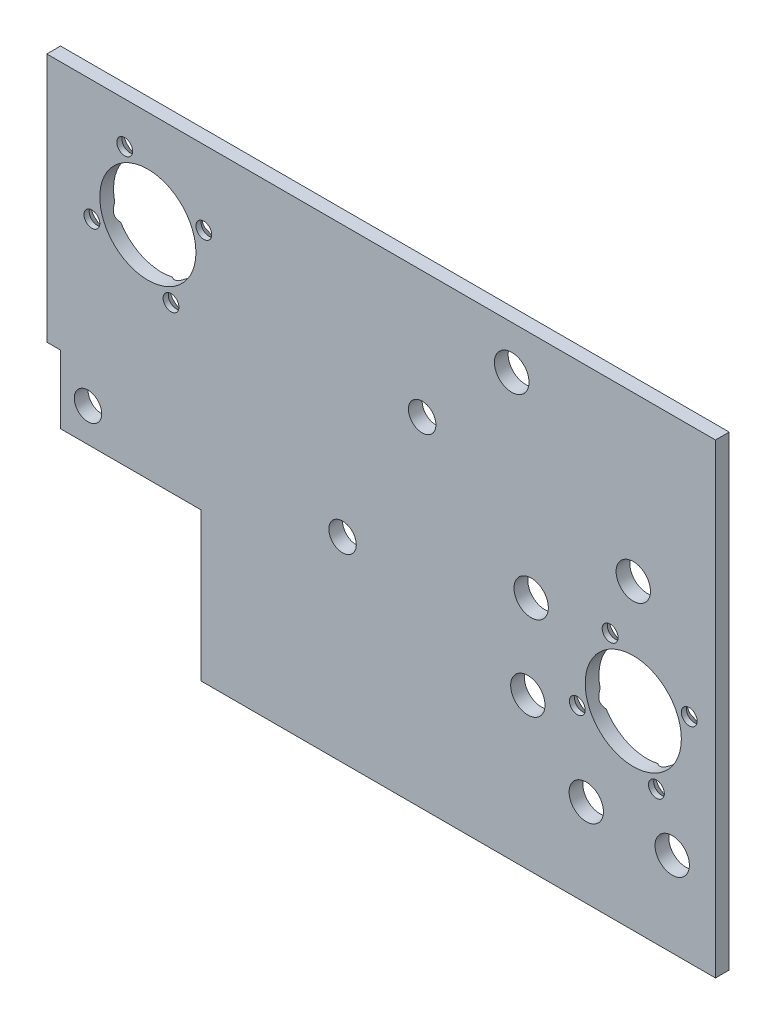
SolidWorks part; units mm, degrees
material "6061-T6 (SS)"
ref_plane "Front" through (0, 0, 0) normal (0, 0, 1) x (1, 0, 0)
ref_plane "Top" through (0, 0, 0) normal (0, 1, 0) x (1, 0, 0)
ref_plane "Right" through (0, 0, 0) normal (1, 0, 0) x (0, 0, -1)
ref_axis "side-side" through (80.9, 0, 0) along (-1, 0, 0)
ref_axis "up-down" through (0, 50, 0) along (0, -1, 0)
ref_axis "front-back" through (0, 0, -80.9) along (0, 0, 1)
sketch "Sketch2" plane through (0, 0, 0) normal (0, 0, 1) x (1, 0, 0)
  line L1 (70.9123, -1.5429) -> (62.6056, 2.3306)
  line L2 (62.6056, 2.3306) -> (55.0977, -2.9265)
  line L3 (55.0977, -2.9265) -> (55.8965, -12.0571)
  line L4 (55.8965, -12.0571) -> (64.2032, -15.9306)
  line L5 (64.2032, -15.9306) -> (71.7111, -10.6735)
  line L12 (71.7111, -10.6735) -> (70.9123, -1.5429)
  line L13 (50, 0) -> (-50, 0) construction
  line L18 (37.0625, -35.4173) -> (37.0625, -44.5827)
  line L19 (45, -30.8346) -> (37.0625, -35.4173)
  line L20 (52.9375, -35.4173) -> (45, -30.8346)
  line L21 (52.9375, -44.5827) -> (52.9375, -35.4173)
  line L22 (45, -49.1654) -> (52.9375, -44.5827)
  line L23 (37.0625, -44.5827) -> (45, -49.1654)
  line L30 (-20.1841, -46.8662) -> (-13.8341, -50.5323)
  line L31 (-20.1841, -39.5338) -> (-20.1841, -46.8662)
  line L32 (-13.8341, -35.8677) -> (-20.1841, -39.5338)
  line L33 (-7.4841, -39.5338) -> (-13.8341, -35.8677)
  line L34 (-7.4841, -46.8662) -> (-7.4841, -39.5338)
  line L35 (-13.8341, -50.5323) -> (-7.4841, -46.8662)
  line L38 (-20.1841, -57.2) -> (-20.1841, -35.2)
  line L39 (-20.1841, -35.2) -> (-23.3591, -35.2)
  line L41 (-23.3591, 24.85) -> (-23.3591, -35.2)
  line L43 (-17.6841, -85.2) -> (393.3159, -85.2)
  line L50 (-20.1841, -51.2) -> (-18.1841, -51.2)
  line L51 (9.8159, -51.2) -> (11.8159, -51.2)
  line L55 (9.8159, -81.2) -> (9.8159, -53.7)
  line L56 (-18.1841, -81.2) -> (9.8159, -81.2)
  line L57 (-18.1841, -53.7) -> (-18.1841, -81.2)
  line L61 (-20.1841, -80.7) -> (-20.1841, -53.7)
  line L62 (9.3159, -83.2) -> (-17.6841, -83.2)
  line L63 (11.8159, -80.7) -> (11.8159, -53.7)
  circle A2 centre (112.2, -41.275) radius 17.272
  circle A3 centre (45, -40) radius 3.175
  circle A5 centre (-13.8341, -43.2) radius 3.175
  circle A6 centre (125.1364, -35.9226) radius 1.25
  circle A7 centre (63.4044, -6.8) radius 7.9375 construction
  circle A9 centre (106.8476, -28.3386) radius 1.25
  circle A13 centre (84.1028, 12.5) radius 4
  circle A22 centre (137.9182, -37.5962) radius 2.6162
  circle A24 centre (127.7842, -20.4882) radius 2.6162
  point P1 (0, 0)
  point P39 (0, 0)
  point P42 (0, 0)
  point P47 (0, 0)
  dimension "D1" = 15.875
  dimension "D2" = 35
sketch "Sketch1" plane through (0, 0, 0) normal (0, 0, 1) x (1, 0, 0)
  line L0 (142.0908, -41.7813) -> (132.1091, -24.584) construction
  line L1 (0, 0) -> (-28.1303, 0) construction
  line L2 (-23.3591, 24.85) -> (-23.3591, -35.2) construction
  line L3 (-23.3591, 22.5) -> (131.2, 22.5)
  line L4 (-23.3591, -35.2) -> (-23.3591, 22.5)
  line L5 (131.2, 22.5) -> (131.2, -85.2)
  line L6 (12.3159, -85.2) -> (131.2, -85.2)
  line L7 (-20.1841, -57.2) -> (-20.1841, -35.2) construction
  line L8 (0, 0) -> (-5.3524, 12.9364) construction
  line L9 (112.2, -41.275) -> (106.8476, -28.3386) construction
  line L10 (112.2, -41.275) -> (99.2636, -46.6274) construction
  line L11 (-20.1841, -35.2) -> (-23.3591, -35.2) construction
  line L12 (-20.1841, -50.95) -> (-20.1841, -35.2)
  line L13 (-20.1841, -35.2) -> (-23.3591, -35.2)
  line L14 (-20.1841, -50.95) -> (12.3159, -50.95)
  line L15 (-20.1841, -51.2) -> (-18.1841, -51.2) construction
  line L16 (88.6029, -30.4058) -> (87.8287, -50.275) construction
  line L17 (12.3159, -50.95) -> (12.3159, -85.2)
  line L18 (11.8159, -80.7) -> (11.8159, -53.7) construction
  line L19 (-17.6841, -85.2) -> (393.3159, -85.2) construction
  line L20 (87.8287, -50.275) -> (101.3308, -64.8721) construction
  line L21 (101.3308, -64.8721) -> (121.2, -65.6463) construction
  circle A0 centre (0, 0) radius 14 construction
  circle A1 centre (0, 0) radius 11.1125
  circle A2 centre (-5.3524, 12.9364) radius 1.8542 construction
  circle A3 centre (-12.9364, -5.3524) radius 1.8542 construction
  circle A4 centre (12.9364, 5.3524) radius 1.8542 construction
  circle A5 centre (5.3524, -12.9364) radius 1.8542 construction
  circle A6 centre (112.2, -41.275) radius 11.1125
  circle A7 centre (-13.8341, -43.2) radius 3.175 construction
  circle A8 centre (106.8476, -28.3386) radius 1.8542 construction
  circle A9 centre (99.2636, -46.6274) radius 1.8542 construction
  circle A10 centre (117.5524, -54.2114) radius 1.8542 construction
  circle A11 centre (125.1364, -35.9226) radius 1.8542 construction
  circle A12 centre (45, -40) radius 3.175 construction
  circle A14 centre (-13.8341, -43.2) radius 3.175
  circle A15 centre (45, -40) radius 3.175
  circle A16 centre (63.4044, -6.8) radius 3.175
  circle A17 centre (88.6029, -30.4058) radius 3.9688
  arc A18 (86.6738, -36.4402) -> (132.1091, -24.584) centre (112.2, -41.275) cw construction
  circle A19 centre (112.2, -15.295) radius 3.9687
  circle A20 centre (84.1028, 12.5) radius 4 construction
  circle A21 centre (87.8287, -50.275) radius 3.9687
  circle A22 centre (101.3308, -64.8721) radius 3.9687
  circle A23 centre (121.2, -65.6463) radius 3.9688
  circle A24 centre (84.1028, 12.5) radius 4
  point P38 (0, 0)
  point P51 (63.4044, -6.8)
  dimension "D1" = 22.225
  dimension "D2" = 3.7084
  dimension "D4" = 43.925
  dimension "D5" = 85.2
  dimension "D6" = 19
  dimension "D7" = 131.2
  dimension "D8" = 10
  dimension "D10" = 28
  dimension "D15" = 7.9375
  dimension "D16" = 42.5971
  dimension "D20" = 25.98
  dimension "D21" = 10
  dimension "D3" = 23.3591
  dimension "D9" = 67.523
  dimension "D11" = 90
  dimension "D12" = 107.7
  dimension "D13" = 0.25
  dimension "D14" = 0.5
  dimension "D17" = 45
  dimension "D18" = 41.275
  dimension "D19" = 112.2
extrude "Boss-Extrude1" add sketch "Sketch1" against normal blind 3.175
hole_wizard "CSK for #6 Flat Head Machine Screw1" positions "Sketch3" profile "Sketch4" countersink size "#6" standard "ANSI Inch"
sketch "Sketch3" plane through (0, 0, -3.175) normal (0, 0, -1) x (-1, 0, 0)
  point P0 (-125.1364, -35.9226)
  point P3 (-106.8476, -28.3386)
  point P6 (-99.2636, -46.6274)
  point P9 (-117.5524, -54.2114)
  point P12 (-5.3524, -12.9364)
  point P15 (-12.9364, 5.3524)
  point P18 (5.3524, 12.9364)
  point P21 (12.9364, -5.3524)
sketch "Sketch4" plane through (125.1364, -35.9226, -3.175) normal (1, 0, 0) x (0, 1, 0)
  line L0 (0, 0) -> (0, 9.0989)
  line L1 (0, 9.0989) -> (1.8288, 8)
  line L2 (1.8288, 8) -> (1.8288, 1.9723)
  line L3 (1.8288, 1.9723) -> (3.5433, 0)
  line L5 (3.5433, 0) -> (0, 0)
  line L6 (-1.8288, 1.9723) -> (-3.5433, 0) construction
  line L10 (0, 9.0989) -> (-1.8288, 8) construction
  line L11 (0, -6.35) -> (0, 107.95) construction
  dimension "Hole Dia." = 3.6576
  dimension "Hole Depth" = 8
  dimension "Near C'Sink Dia." = 7.0866
  dimension "Near C'Sink Angle" = 82
  dimension "Drill Angle" = 118
